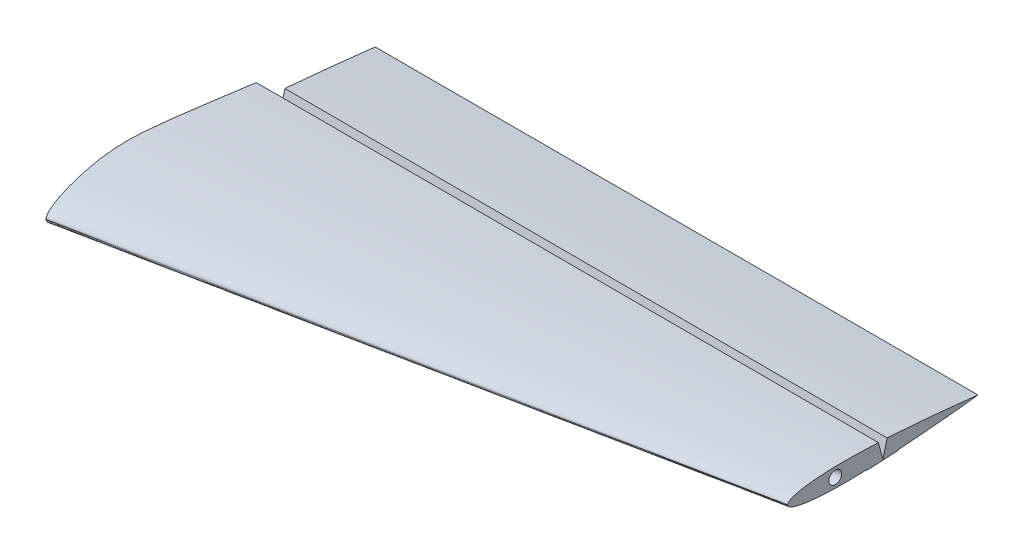
SolidWorks part; units mm, degrees
ref_plane "Front Plane" through (0, 0, 0) normal (0, 0, 1) x (1, 0, 0)
ref_plane "Top Plane" through (0, 0, 0) normal (0, 1, 0) x (1, 0, 0)
ref_plane "Right Plane" through (0, 0, 0) normal (1, 0, 0) x (0, 0, -1)
sketch "0010 template"
sketch_block_instance "Block2-1"
sketch_block "Block2"
sketch "Sketch4" plane through (0, 0, 0) normal (1, 0, 0) x (0, 0, -1)
  line L0 (0, 0) -> (-250, 0) construction
  spline S0 degree 4 poles (-250, 0) (-249.9999, 0.1958) (-249.9612, 0.6039) (-249.7596, 1.2633) (-249.1282, 2.2398) (-248.1098, 3.1752) (-246.5761, 4.1828) (-244.1271, 5.3667) (-240.0739, 6.8179) (-232.84, 8.6113) (-221.2945, 10.4497) (-205.8077, 11.8178) (-187.4923, 12.5325) (-167.6157, 12.5624) (-147.9613, 12.1042) (-127.9831, 11.2209) (-108.5655, 10.1073) (-88.2725, 8.6479) (-69.4578, 7.1641) (-48.2492, 5.205) (-31.0441, 3.5474) (-5.6278, 0.7144) (5.3818, -0.6305) (19.3913, -2.4508) (24.9342, -3.2323) knots 0 0 0 0 0 0.002791 0.005883 0.009735 0.016522 0.022438 0.032158 0.048634 0.078249 0.129037 0.199997 0.270957 0.341918 0.412878 0.483838 0.554798 0.625759 0.696719 0.767679 0.83864 0.9096 1 1 1 1 1 construction
  spline S1 degree 4 poles (-250, 0) (-249.9999, 0.1958) (-249.9612, 0.6039) (-249.7596, 1.2633) (-249.1282, 2.2398) (-248.1098, 3.1752) (-246.5761, 4.1828) (-244.1271, 5.3667) (-240.0739, 6.8179) (-232.84, 8.6113) (-221.2945, 10.4497) (-205.8077, 11.8178) (-187.4923, 12.5325) (-167.6157, 12.5624) (-147.9613, 12.1042) (-127.9831, 11.2209) (-108.5655, 10.1073) (-88.2725, 8.6479) (-69.4578, 7.1641) (-48.2492, 5.205) (-31.0441, 3.5474) (-13.2038, 1.5588) (-4.4672, 0.5411) (0, 0) knots 0 0 0 0 0 0.002791 0.005883 0.009735 0.016522 0.022438 0.032158 0.048634 0.078249 0.129037 0.199997 0.270957 0.341918 0.412878 0.483838 0.554798 0.625759 0.696719 0.767679 0.83864 0.9096 0.9096 0.9096 0.9096 0.9096
  spline S2 degree 4 poles (-250, 0) (-249.9999, -0.1958) (-249.9612, -0.6039) (-249.7596, -1.2633) (-249.1282, -2.2398) (-248.1098, -3.1752) (-246.5761, -4.1828) (-244.1271, -5.3667) (-240.0739, -6.8179) (-232.84, -8.6113) (-221.2945, -10.4497) (-205.8077, -11.8178) (-187.4923, -12.5325) (-167.6157, -12.5624) (-147.9613, -12.1042) (-127.9831, -11.2209) (-108.5655, -10.1073) (-88.2725, -8.6479) (-69.4578, -7.1641) (-48.2492, -5.205) (-31.0441, -3.5474) (-13.2038, -1.5588) (-4.4672, -0.5411) (0, 0) knots 0 0 0 0 0 0.002791 0.005883 0.009735 0.016522 0.022438 0.032158 0.048634 0.078249 0.129037 0.199997 0.270957 0.341918 0.412878 0.483838 0.554798 0.625759 0.696719 0.767679 0.83864 0.9096 0.9096 0.9096 0.9096 0.9096
ref_plane "Plane1" through (500, 0, 0) normal (1, 0, 0) x (0, 0, -1)
sketch "Sketch7" plane through (500, 0, 0) normal (1, 0, 0) x (0, 0, -1)
  line L0 (0, 0) -> (-150, 0) construction
  spline S0 degree 4 poles (-150, 0) (-149.9999, 0.1175) (-149.9767, 0.3624) (-149.8557, 0.758) (-149.4769, 1.3439) (-148.8659, 1.9051) (-147.9457, 2.5097) (-146.4763, 3.22) (-144.0443, 4.0908) (-139.704, 5.1668) (-132.7767, 6.2698) (-123.4846, 7.0907) (-112.4954, 7.5195) (-100.5694, 7.5374) (-88.7768, 7.2625) (-76.7899, 6.7325) (-65.1393, 6.0644) (-52.9635, 5.1887) (-41.6747, 4.2985) (-28.9495, 3.123) (-18.6265, 2.1284) (-3.3767, 0.4286) (3.2291, -0.3783) (11.6348, -1.4705) (14.9605, -1.9394) knots 0 0 0 0 0 0.002791 0.005883 0.009735 0.016522 0.022438 0.032158 0.048634 0.078249 0.129037 0.199997 0.270957 0.341918 0.412878 0.483838 0.554798 0.625759 0.696719 0.767679 0.83864 0.9096 1 1 1 1 1 construction
  spline S1 degree 4 poles (-150, 0) (-149.9999, 0.1175) (-149.9767, 0.3624) (-149.8557, 0.758) (-149.4769, 1.3439) (-148.8659, 1.9051) (-147.9457, 2.5097) (-146.4763, 3.22) (-144.0443, 4.0908) (-139.704, 5.1668) (-132.7767, 6.2698) (-123.4846, 7.0907) (-112.4954, 7.5195) (-100.5694, 7.5374) (-88.7768, 7.2625) (-76.7899, 6.7325) (-65.1393, 6.0644) (-52.9635, 5.1887) (-41.6747, 4.2985) (-28.9495, 3.123) (-18.6265, 2.1284) (-7.9223, 0.9353) (-2.6803, 0.3247) (0, 0) knots 0 0 0 0 0 0.002791 0.005883 0.009735 0.016522 0.022438 0.032158 0.048634 0.078249 0.129037 0.199997 0.270957 0.341918 0.412878 0.483838 0.554798 0.625759 0.696719 0.767679 0.83864 0.9096 0.9096 0.9096 0.9096 0.9096
  spline S2 degree 4 poles (-150, 0) (-149.9999, -0.1175) (-149.9767, -0.3624) (-149.8557, -0.758) (-149.4769, -1.3439) (-148.8659, -1.9051) (-147.9457, -2.5097) (-146.4763, -3.22) (-144.0443, -4.0908) (-139.704, -5.1668) (-132.7767, -6.2698) (-123.4846, -7.0907) (-112.4954, -7.5195) (-100.5694, -7.5374) (-88.7768, -7.2625) (-76.7899, -6.7325) (-65.1393, -6.0644) (-52.9635, -5.1887) (-41.6747, -4.2985) (-28.9495, -3.123) (-18.6265, -2.1284) (-7.9223, -0.9353) (-2.6803, -0.3247) (0, 0) knots 0 0 0 0 0 0.002791 0.005883 0.009735 0.016522 0.022438 0.032158 0.048634 0.078249 0.129037 0.199997 0.270957 0.341918 0.412878 0.483838 0.554798 0.625759 0.696719 0.767679 0.83864 0.9096 0.9096 0.9096 0.9096 0.9096
  dimension "D1" = 0
loft "Loft2" add profiles "Sketch7", "Sketch4" connector at (500, 0, 150) connector at (0, 0, 250)
sketch "Sketch8" plane through (0, 0, 0) normal (-1, 0, 0) x (0, 0, 1)
  line L0 (0, 0) -> (250, 0) construction
  line L1 (75, 0) -> (75, -7.293) construction
  line L2 (75, -7.293) -> (70.1733, 10.7205)
  line L3 (70.1733, 10.7205) -> (79.8267, 10.7205)
  line L4 (79.8267, 10.7205) -> (75, -7.293)
  dimension "D1" = 75
  dimension "D2" = 15
  dimension "D3" = 15
sketch "Sketch9" plane through (500, 0, 0) normal (1, 0, 0) x (0, 0, -1)
  line L0 (-150, 0) -> (0, 0) construction
  line L1 (-75, 0) -> (-75, -6.3837) construction
  line L2 (-75, -6.3837) -> (-79.0924, 8.8893)
  line L3 (-79.0924, 8.8893) -> (-70.9076, 8.8893)
  line L4 (-70.9076, 8.8893) -> (-75, -6.3837)
  dimension "D1" = 15
  dimension "D2" = 15
  dimension "D3" = 75
loft "Cut-Loft1" cut profiles "Sketch9", "Sketch8" connector at (500, 8.8893, 70.9076) connector at (0, 10.7205, 70.1733)
sketch "Sketch12" plane through (0, 0, 0) normal (-1, 0, 0) x (0, 0, 1)
  line L0 (137.5, 0) -> (-137.5, 0) construction
  point P0 (187.5, 0)
  dimension "D1" = 62.5
sketch "Sketch13" plane through (500, 0, 0) normal (1, 0, 0) x (0, 0, -1)
  line L0 (137.5, 0) -> (-137.5, 0) construction
  point P0 (-112.5, 0)
  dimension "D1" = 37.5
ref_axis "Axis1" through (500, 0, 112.5) along (-0.9889, 0, 0.1483)
ref_plane "Plane2" through (500, 0, 112.5) normal (-0.9889, 0, 0.1483) x (0.1483, 0, 0.9889)
sketch "Sketch14" plane through (500, 0, 112.5) normal (-0.9889, 0, 0.1483) x (0.1483, 0, 0.9889)
  circle A0 centre (0, 0) radius 5
  dimension "D1" = 10
extrude "Cut-Extrude3" cut sketch "Sketch14" against normal through all and the other way through all
sketch "Sketch10" plane through (0, 0, 0) normal (0, 1, 0) x (1, 0, 0)
  line L0 (500, 0) -> (0, 0) construction
  line L1 (25, 0) -> (0, 0)
  line L2 (25, 0) -> (25, -79.0722)
  line L3 (25, -79.0722) -> (0, -79.0722)
  line L4 (0, 0) -> (0, -79.0722)
  line L5 (0, -13.8186) -> (0, 13.8186) construction
  spline S0 degree 3 poles (500, -78.5288) (416.6672, -78.6598) (333.3338, -78.7555) (166.667, -78.9261) (83.3335, -79.0019) (0, -79.0722) knots 0 0 0 0 0.5 0.5 1 1 1 1 construction
  dimension "D1" = 25
extrude "Cut-Extrude1" cut sketch "Sketch10" against normal through all and the other way through all
sketch "Sketch11" plane through (0, 0, 0) normal (0, 0, 1) x (1, 0, 0)
  circle A0 centre (0, 0) radius 13
  dimension "D1" = 26
extrude "Cut-Extrude2" cut sketch "Sketch11" along normal through all
ref_axis "Axis2" through (25, -7.2475, 75) along (1, 0.0018, 0)
sketch "Sketch16" plane through (0, 0, 0) normal (0, 1, 0) x (1, 0, 0)
  line L0 (25, -75) -> (500, -75) construction
  line L1 (30, -95) -> (74, -95)
  line L2 (30, -95) -> (30, -139)
  line L3 (30, -139) -> (74, -139)
  line L4 (74, -95) -> (74, -139)
  dimension "D1" = 44
  dimension "D2" = 44
  dimension "D3" = 20
  dimension "D4" = 5
extrude "Cut-Extrude4" cut sketch "Sketch16" against normal through all and the other way blind 5.2
sketch "Sketch17" plane through (500, 0, 0) normal (1, 0, 0) x (0, 0, -1)
  line L0 (-87.4762, -7.1658) -> (-62.4762, -5.8528)
  line L1 (-62.4762, -5.8528) -> (-62.4499, -6.3521)
  line L2 (-62.4499, -6.3521) -> (-87.4499, -7.6651)
  line L3 (-87.4499, -7.6651) -> (-87.4762, -7.1658)
  spline S0 degree 4 poles (-150, 0) (-149.9999, -0.1175) (-149.9767, -0.3624) (-149.8557, -0.758) (-149.4769, -1.3439) (-148.8659, -1.9051) (-147.9457, -2.5097) (-146.4763, -3.22) (-144.0443, -4.0908) (-139.704, -5.1668) (-132.7767, -6.2698) (-123.4846, -7.0907) (-112.4954, -7.5195) (-100.5694, -7.5374) (-88.7768, -7.2625) (-76.7899, -6.7325) (-65.1393, -6.0644) (-52.9635, -5.1887) (-41.6747, -4.2985) (-28.9495, -3.123) (-18.6265, -2.1284) (-7.9223, -0.9353) (-2.6803, -0.3247) (0, 0) knots 0 0 0 0 0 0.002791 0.005883 0.009735 0.016522 0.022438 0.032158 0.048634 0.078249 0.129037 0.199997 0.270957 0.341918 0.412878 0.483838 0.554798 0.625759 0.696719 0.767679 0.83864 0.9096 0.9096 0.9096 0.9096 0.9096 construction
  dimension "D1" = 12.5
  dimension "D2" = 25
  dimension "D3" = 25
  dimension "D4" = 0.5
sketch "Sketch18" plane through (25, 0, 0) normal (-1, 0, 0) x (0, 0, 1)
  line L0 (62.5202, -6.4828) -> (87.5202, -8.5817)
  line L1 (87.5202, -8.5817) -> (87.4782, -9.0817)
  line L2 (87.4782, -9.0817) -> (62.4782, -6.9828)
  line L3 (62.4782, -6.9828) -> (62.5202, -6.4828)
  spline S0 degree 4 poles (0, 0) (4.3779, -0.5303) (12.9397, -1.5276) (30.4233, -3.4764) (47.2842, -5.1009) (63.3693, -6.5868) (73.3998, -7.4221) (78.617, -7.8365) (79.0722, -7.8725) knots 0 0 0 0 0 0.078013 0.156025 0.234038 0.312051 0.319509 0.319509 0.319509 0.319509 0.319509 construction
  dimension "D1" = 12.5
  dimension "D2" = 0.5
  dimension "D3" = 25
loft "Loft3" add profiles "Sketch18", "Sketch17" connector at (25, -9.0817, 87.4782) connector at (500, -7.6651, 87.4499)
